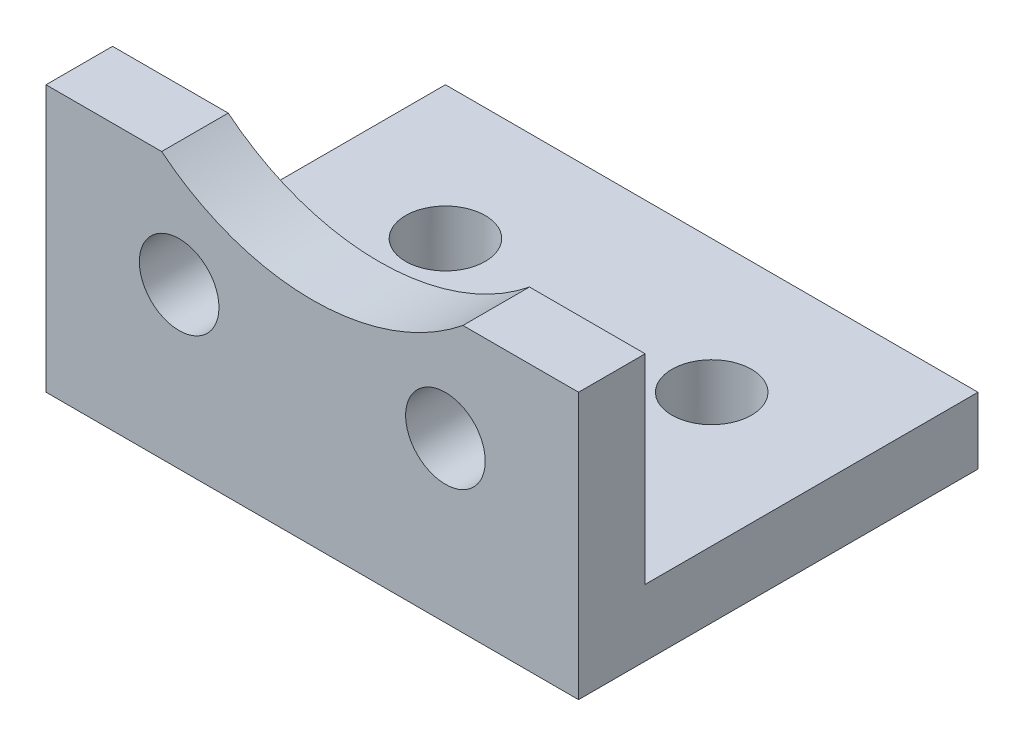
SolidWorks part; units mm, degrees
material "6061 Alloy"
ref_plane "Front Plane" through (0, 0, 0) normal (0, 0, 1) x (1, 0, 0)
ref_plane "Top Plane" through (0, 0, 0) normal (0, 1, 0) x (1, 0, 0)
ref_plane "Right Plane" through (0, 0, 0) normal (1, 0, 0) x (0, 0, -1)
sketch "Sketch2" plane through (0, 0, 0) normal (1, 0, 0) x (0, 0, -1)
  line L0 (0, 0) -> (0, 12.7)
  line L1 (0, 12.7) -> (3.175, 12.7)
  line L2 (3.175, 12.7) -> (3.175, 3.175)
  line L3 (3.175, 3.175) -> (19.05, 3.175)
  line L4 (19.05, 3.175) -> (19.05, 0)
  line L5 (19.05, 0) -> (0, 0)
  line L6 (0, 0) -> (0.1044, -0.0877)
  dimension "D1" = 19.05
  dimension "D2" = 12.7
  dimension "D3" = 3.175
  dimension "D4" = 3.175
extrude "Extrude1" add sketch "Sketch2" along normal blind 12.7 and the other way blind 12.7 contours L0 L1 L2 L3 L4 L5
hole_wizard "#6 Clearance Hole1" positions "3DSketch1" profile "Sketch3" hole size "#6" standard "Ansi Inch"
sketch3d "3DSketch1"
  line L0 (12.7, 12.7, -3.175) -> (-12.7, 12.7, -3.175) construction
  line L1 (12.7, 3.175, -19.05) -> (-12.7, 3.175, -19.05) construction
  line L3 (12.7, 12.7, -3.175) -> (12.7, 3.175, -3.175) construction
  line L6 (12.7, 3.175, -3.175) -> (12.7, 3.175, -19.05) construction
  point P0 (6.35, 7.62, -3.175)
  point P6 (6.35, 3.175, -12.7)
  point P24 (-6.35, 3.175, -12.7)
  point P26 (-6.35, 7.62, -3.175)
  dimension "D1" = 5.08
  dimension "D2" = 12.7
  dimension "D3" = 12.7
  dimension "D4" = 6.35
  dimension "D5" = 6.35
  dimension "D8" = 6.35
sketch "Sketch3" plane through (6.35, 7.62, -3.175) normal (1, 0, 0) x (0, 1, 0)
  line L0 (0, 0) -> (0, 13.8408)
  line L1 (0, 13.8408) -> (1.8986, 12.7)
  line L2 (1.8986, 12.7) -> (1.8986, 0)
  line L5 (1.8986, 0) -> (0, 0)
  line L10 (0, 13.8408) -> (-1.8987, 12.7) construction
  line L11 (0, -6.35) -> (0, 107.95) construction
  dimension "Hole Dia." = 3.7973
  dimension "Hole Depth" = 12.7
  dimension "Drill Angle" = 118
sketch "Sketch4" plane through (0, 0, -3.175) normal (0, 0, -1) x (-1, 0, 0)
  line L0 (12.7, 12.7) -> (12.7, 3.175) construction
  line L1 (-12.7, 3.175) -> (12.7, 3.175) construction
  circle A0 centre (0, 21.59) radius 11.43
  circle A1 centre (-6.35, 7.62) radius 1.8986 construction
  dimension "D3" = 22.86
  dimension "D4" = 13.97
  dimension "D1" = 12.7
  dimension "D2" = 18.415
extrude "Cut-Extrude1" cut sketch "Sketch4" against normal through all
